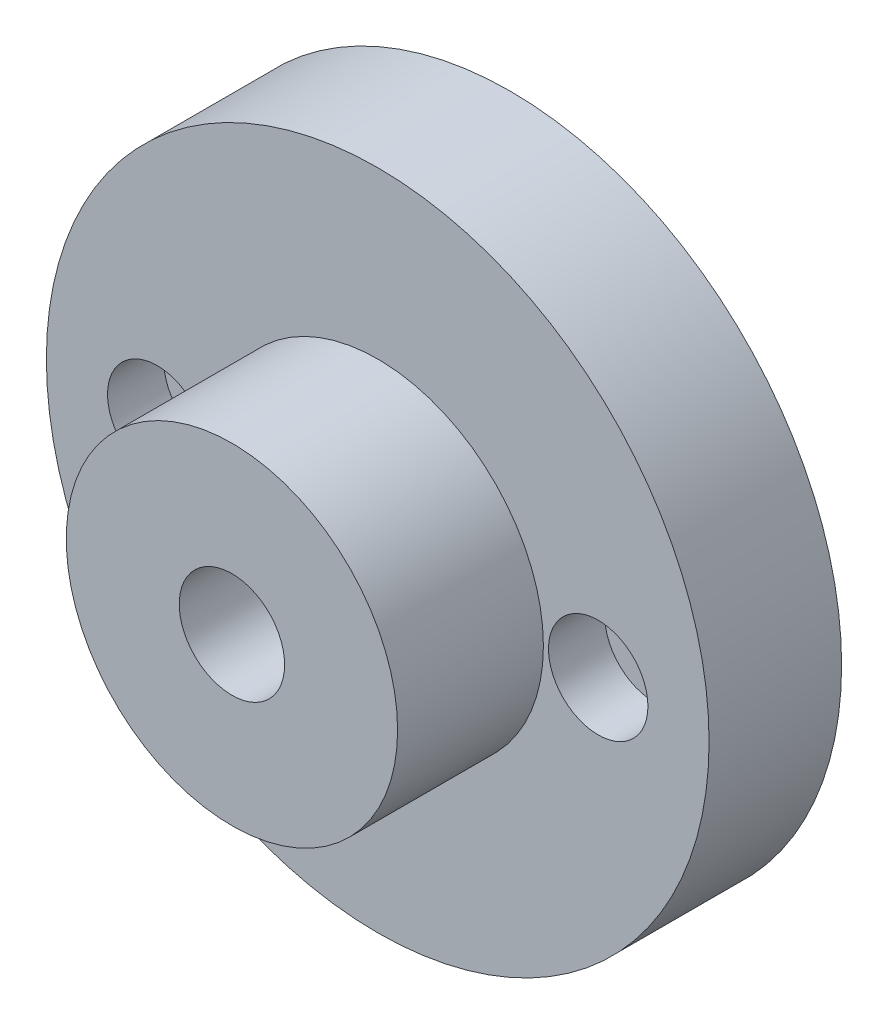
SolidWorks part; units mm, degrees
ref_plane "Front Plane" through (0, 0, 0) normal (0, 0, 1) x (1, 0, 0)
ref_plane "Top Plane" through (0, 0, 0) normal (0, 1, 0) x (1, 0, 0)
ref_plane "Right Plane" through (0, 0, 0) normal (1, 0, 0) x (0, 0, -1)
sketch "Sketch1" plane through (0, 0, 0) normal (0, 0, 1) x (1, 0, 0)
  circle A0 centre (0, 0) radius 12.7
  dimension "D1" = 25.4
extrude "Boss-Extrude1" add sketch "Sketch1" along normal blind 5.08
sketch "Sketch3" plane through (0, 0, 5.08) normal (0, 0, 1) x (1, 0, 0)
  circle A0 centre (0, 0) radius 6.35
  dimension "D1" = 12.7
extrude "Boss-Extrude2" add sketch "Sketch3" along normal blind 5.588
sketch "Sketch5" plane through (0, 0, 10.668) normal (0, 0, 1) x (1, 0, 0)
  circle A0 centre (0, 0) radius 2.0193
  dimension "D1" = 4.0386
extrude "Cut-Extrude1" cut sketch "Sketch5" against normal blind 5.588
sketch "Sketch6" plane through (0, 0, 5.08) normal (0, 0, 1) x (1, 0, 0)
  circle A0 centre (-8.4506, 0) radius 1.905
  circle A1 centre (8.4506, 0) radius 1.905
  point P0 (-8.4506, 0)
  point P1 (8.4506, 0)
  dimension "D3" = 3.81
  dimension "D4" = 3.81
  dimension "D1" = 8.4506
  dimension "D2" = 8.4506
hole_wizard "#50 (0.07) Diameter Hole1" positions "Sketch7" profile "Sketch8" hole size "#50" standard "ANSI Inch" end condition through all
sketch "Sketch7" plane through (0, 0, 5.08) normal (0, 0, 1) x (1, 0, 0)
  point P0 (-8.4506, 0)
  point P3 (8.4506, 0)
  dimension "D1" = 8.4506
  dimension "D2" = 8.4506
  dimension "D3" = 16.9012
sketch "Sketch8" plane through (-8.4506, 0, 5.08) normal (1, 0, 0) x (0, -1, 0)
  line L0 (0, 0) -> (0, 5.08)
  line L1 (0, 5.08) -> (0.889, 5.08)
  line L2 (0.889, 5.08) -> (0.889, 0)
  line L5 (0.889, 0) -> (0, 0)
  line L11 (0, -6.35) -> (0, 107.95) construction
  dimension "Thru Hole Dia." = 1.778
  dimension "Thru Hole Depth" = 5.08
extrude "Cut-Extrude2" cut sketch "Sketch6" against normal blind 2.159
sketch "Sketch9" plane through (0, 0, 0) normal (0, 0, -1) x (-1, 0, 0)
  circle A0 centre (-1.999, 0) radius 1.905
  circle A1 centre (-8.4506, 0) radius 0.889 construction
  dimension "D1" = 3.81
  dimension "D2" = 6.4516
extrude "Cut-Extrude3" cut sketch "Sketch9" against normal through all draft 45
